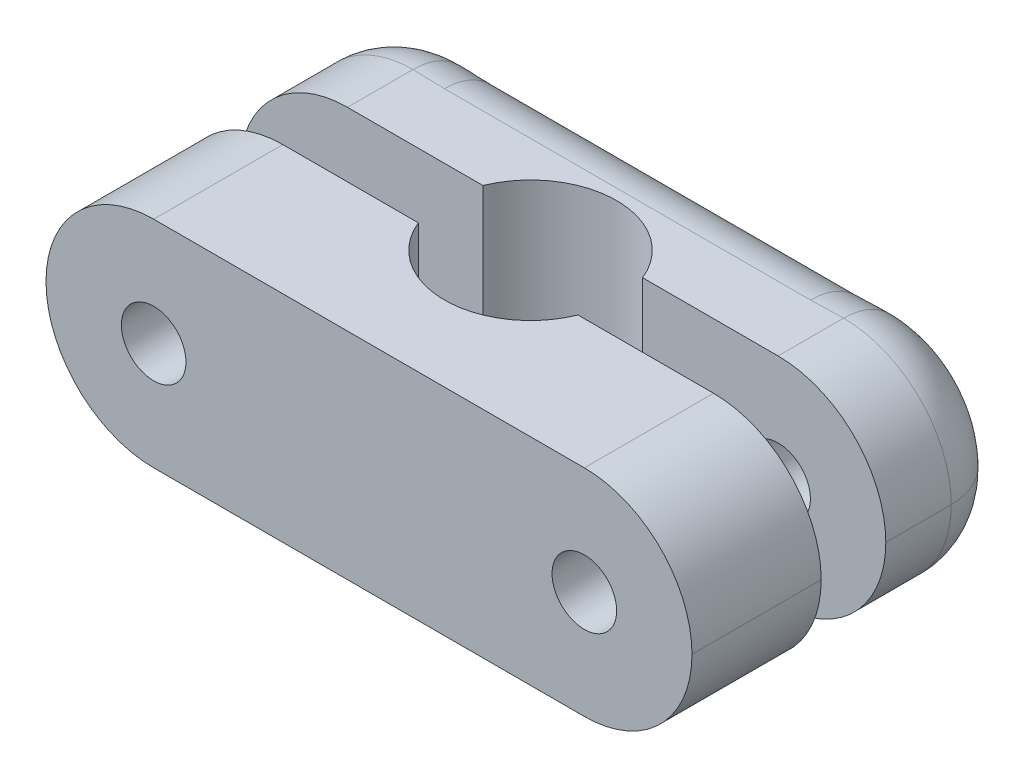
SolidWorks part; units mm, degrees
material "ABS"
ref_plane "Front Plane" through (0, 0, 0) normal (0, 0, 1) x (1, 0, 0)
ref_plane "Top Plane" through (0, 0, 0) normal (0, 1, 0) x (1, 0, 0)
ref_plane "Right Plane" through (0, 0, 0) normal (1, 0, 0) x (0, 0, -1)
sketch "Sketch1" plane through (0, 0, 0) normal (0, 1, 0) x (1, 0, 0)
  line L1 (-15, -7.5) -> (15, -7.5)
  line L2 (-15, -7.5) -> (-15, 7.5)
  line L3 (-15, 7.5) -> (15, 7.5)
  line L4 (15, -7.5) -> (15, 7.5)
  line L5 (-15, -7.5) -> (15, 7.5) construction
  line L6 (-15, 7.5) -> (15, -7.5) construction
  point P0 (0, 0)
  dimension "D1" = 30
  dimension "D2" = 15
extrude "Boss-Extrude1" add sketch "Sketch1" along normal blind 10
sketch "Sketch2" plane through (0, 10, 0) normal (0, 1, 0) x (1, 0, 0)
  circle A0 centre (0, 0) radius 4
  dimension "D1" = 8
extrude "Cut-Extrude1" cut sketch "Sketch2" against normal blind 10
sketch "Sketch3" plane through (0, 0, 7.5) normal (0, 0, 1) x (1, 0, 0)
  line L0 (-15, 0) -> (15, 0) construction
  line L1 (-15, 10) -> (-15, 0) construction
  circle A0 centre (-10, 5) radius 1.5
  circle A1 centre (10, 5) radius 1.5
  dimension "D1" = 3
  dimension "D5" = 3
  dimension "D2" = 5
  dimension "D3" = 5
  dimension "D4" = 20
extrude "Cut-Extrude2" cut sketch "Sketch3" against normal through all
sketch "Sketch4" plane through (0, 0, -7.5) normal (0, 0, -1) x (-1, 0, 0)
  circle A0 centre (-10, 5) radius 2.5
  circle A1 centre (10, 5) radius 2.5
  dimension "D1" = 5
  dimension "D2" = 5
extrude "Cut-Extrude3" cut sketch "Sketch4" against normal blind 3.5
sketch "Sketch5" plane through (0, 10, 0) normal (0, 1, 0) x (1, 0, 0)
  line L0 (-15, 7.5) -> (-15, -7.5) construction
  line L1 (15, 1.5) -> (-15, 1.5)
  line L2 (15, 1.5) -> (15, -1.5)
  line L3 (15, -1.5) -> (-15, -1.5)
  line L4 (-15, 1.5) -> (-15, -1.5)
  line L5 (15, 1.5) -> (-15, -1.5) construction
  line L6 (15, -1.5) -> (-15, 1.5) construction
  point P0 (0, 0)
  dimension "D1" = 3
extrude "Cut-Extrude4" cut sketch "Sketch5" against normal through all
fillet "Fillet3" radius 5 4 edges at (15, 10, 4.5) (15, 0, 4.5) (-15, 0, 4.5) (-15, 10, 4.5)
fillet "Fillet4" radius 5 4 edges at (15, 0, -4.5) (15, 10, -4.5) (-15, 0, -4.5) (-15, 10, -4.5)
fillet "Fillet2" radius 3 2 edges at (0, 10, -7.5) (0, 0, -7.5)
